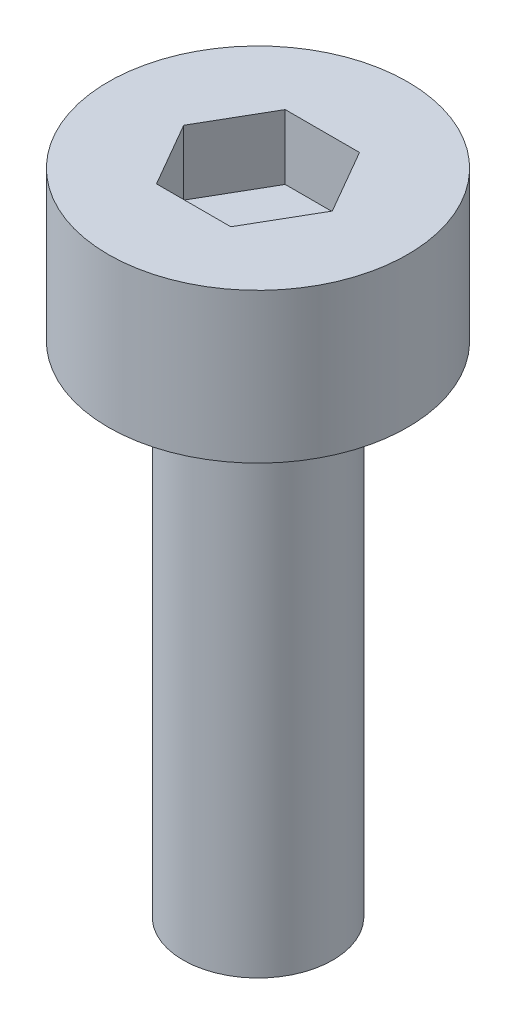
SolidWorks part; units mm, degrees
ref_plane "Front Plane" through (0, 0, 0) normal (0, 0, 1) x (1, 0, 0)
ref_plane "Top Plane" through (0, 0, 0) normal (0, 1, 0) x (1, 0, 0)
ref_plane "Right Plane" through (0, 0, 0) normal (1, 0, 0) x (0, 0, -1)
sketch "Sketch1" plane through (0, 0, 0) normal (0, 1, 0) x (1, 0, 0)
  circle A0 centre (0, 0) radius 1.5
  dimension "D1" = 3
extrude "ScrewShaft" add sketch "Sketch1" along normal blind 10
sketch "Sketch2" plane through (0, 10, 0) normal (0, 1, 0) x (1, 0, 0)
  circle A0 centre (0, 0) radius 3
  dimension "D1" = 6
extrude "Boss-Extrude2" add sketch "Sketch2" along normal blind 3
sketch "Sketch3" plane through (0, 13, 0) normal (0, 1, 0) x (1, 0, 0)
  line L0 (0, 0) -> (0, 1.29) construction
  line L1 (1.4896, 0) -> (0.7448, 1.29)
  line L2 (0.7448, 1.29) -> (-0.7448, 1.29)
  line L3 (-0.7448, 1.29) -> (-1.4896, 0)
  line L4 (-1.4896, 0) -> (-0.7448, -1.29)
  line L5 (-0.7448, -1.29) -> (0.7448, -1.29)
  line L6 (0.7448, -1.29) -> (1.4896, 0)
  circle A0 centre (0, 0) radius 1.29 construction
  dimension "D1" = 2.58
extrude "Cut-Extrude1" cut sketch "Sketch3" against normal blind 1.3
equation "\"X-ROD-SPACING\"=45"
equation "\"Y-ROD-SPACING\"=75"
equation "\"Z-ROD-SPACING\"=17.5"
equation "\"Y-BED-OFFSET\"=2"
equation "\"Y-BED-ROD-INSET\"=3.5"
equation "\"T-SLOT-NUT-FILLET-RADIUS\"=0.25"
equation "\"T-SLOT-SCREW-SHAFT-RADIUS\"=1.75"
equation "\"T-SLOT-SCREW-SHAFT-CUTOUT-LENGTH\"=10.5"
equation "\"T-SLOT-NUT-DEPTH\"=4.2"
equation "\"T-SLOT-NUT-WIDTH\"=3"
equation "\"T-SLOT-NUT-END-DISTANCE\"=8"
equation "\"ACRYLIC-THICKNESS\"=10"
equation "\"ACRYLIC-THICKNESS2\"=4.5"
equation "\"ACRYLIC-TAB-CUTOUT-SIZE\"=\"ACRYLIC-THICKNESS\"+\"ACRYLIC-TAB-TOLERANCE\"*2"
equation "\"ACRYLIC-TAB-WIDTH\"=\"ACRYLIC-THICKNESS\""
equation "\"ACRYLIC-M3-HOLE\"=3.2"
equation "\"SMOOTHROD-CAP-SCREW-DISTANCE\"=20"
equation "\"FRAME-WIDTH-INNER\"=370"
equation "\"NEMA17-HOLE-SPACING\"=31"
equation "\"NEMA17-CENTRAL-CUTOUT\"=22.5"
equation "\"Z-BRACKET-REACH\"=55"
equation "\"TOP-BRACKET-SPACING\"=40"
equation "\"SMOOTHROD-X-LENGTH\"=350"
equation "\"SMOOTHROD-Y-LENGTH\"=350"
equation "\"SMOOTHROD-Z-LENGTH\"=350"
equation "\"SMOOTHROD-TIGHTENING-HEADROOM\"=1"
equation "\"LEADSCREW-Z-LENGTH\"=300"
equation "\"SCREW-LENGTH-FRAME\"=\"ACRYLIC-THICKNESS\" + 10"
equation "\"SCREW-HEAD-RADIUS\"=6"
equation "\"PRINTED-X-SMOOTHROD-DIAMETER\"=8.2"
equation "\"PRINTED-X-SMOOTHROD-CUTOUT\"=10"
equation "\"PRINTED-X-BASE-HEIGHT\"=10"
equation "\"PRINTED-LM8UU-CUTOUT-SIZE\"=16"
equation "\"PRINTED-LM8UU-CUTOUT-LENGTH\"=24.5"
equation "\"PRINTED-X-IDLER-HEIGHT\"=16"
equation "\"PSU-MOUNTING-WIDTH\"=95"
equation "\"PSU-MOUNTING-HEIGHT\"=177"
equation "\"D1@Sketch2\"=\"SCREW-HEAD-RADIUS\""
